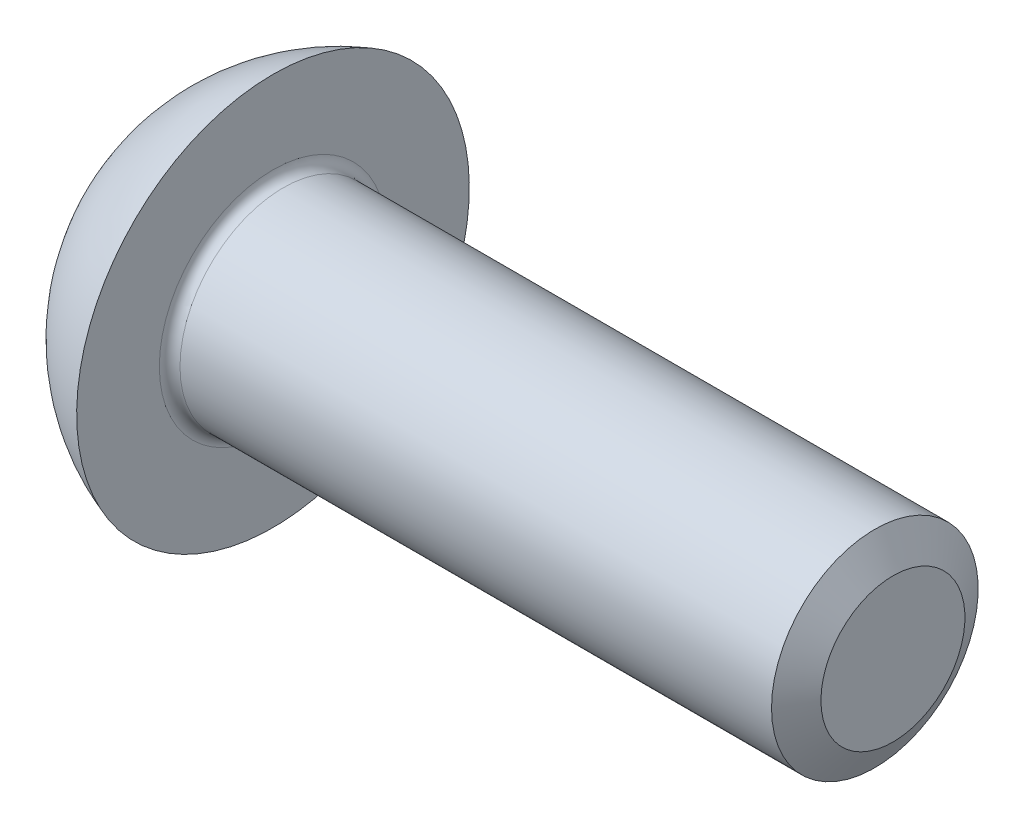
SolidWorks part; units mm, degrees
ref_plane "前视基准面" through (0, 0, 0) normal (0, 0, 1) x (1, 0, 0)
ref_plane "上视基准面" through (0, 0, 0) normal (0, 1, 0) x (1, 0, 0)
ref_plane "右视基准面" through (0, 0, 0) normal (1, 0, 0) x (0, 0, -1)
sketch "尺寸草图" plane through (0, 0, 0) normal (0, 0, 1) x (1, 0, 0)
  line L0 (0, 0) -> (12, 0) construction
  line L1 (12, 0) -> (12, 2) construction
  line L2 (12, 2) -> (11.3, 2) construction
  line L3 (0, 0) -> (0, 3.8) construction
  point P3 (1.4, 0)
  point P6 (12, 2.35)
  point P7 (0, 0.93)
  point P9 (2.2, 0)
  point P10 (2.4, 0)
  point P11 (12, 1.25)
  point P12 (3.7, 0)
  point P13 (4, 0)
  point P14 (12, 14.35)
  dimension "l" = 12
  dimension "d" = 4
  dimension "P" = 0.7
  dimension "a" = 1.4
  dimension "da" = 4.7
  dimension "dk" = 7.6
  dimension "e" = 2.87
  dimension "K" = 2.2
  dimension "r" = 0.2
  dimension "s" = 2.5
  dimension "t" = 1.3
  dimension "w" = 0.3
  dimension "zslwx" = 12
sketch "草图1" plane through (0, 0, 0) normal (0, 0, 1) x (1, 0, 0)
  line L0 (-14.2, 0) -> (0, 0) construction
  line L1 (0, 2) -> (-11.8, 2)
  line L2 (-12, 2.2) -> (-12, 3.8)
  line L3 (-14.2, 0) -> (-14.2, 2)
  line L4 (0, 2) -> (0, 0)
  line L5 (-14.2, 0) -> (0, 0)
  arc A0 (-12, 3.8) -> (-14.2, 2) centre (-10.7273, 0) ccw
  arc A1 (-11.8, 2) -> (-12, 2.2) centre (-11.8, 2.2) cw
  point P10 (-12, 2)
  dimension "r" = 0.2
  dimension "d" = 4
  dimension "dk" = 7.6
  dimension "k" = 2.2
  dimension "l" = 12
revolve "旋转1" add sketch "草图1" angle 360 about L0
cosmetic thread "装饰螺纹线1" parameters "D1"=12, "D2"=3.44
sketch "草图2" plane through (-14.2, 0, 0) normal (-1, 0, 0) x (0, 0, 1)
  line L1 (0, 1.4434) -> (-1.25, 0.7217)
  line L2 (-1.25, 0.7217) -> (-1.25, -0.7217)
  line L3 (-1.25, -0.7217) -> (0, -1.4434)
  line L4 (0, -1.4434) -> (1.25, -0.7217)
  line L5 (1.25, -0.7217) -> (1.25, 0.7217)
  line L6 (1.25, 0.7217) -> (0, 1.4434)
  circle A0 centre (0, 0) radius 1.25 construction
  dimension "s" = 2.5
extrude "切除-拉伸1" cut sketch "草图2" against normal blind 2.2
sketch "草图6" plane through (0, 0, 0) normal (0, 0, 1) x (1, 0, 0)
  line L0 (-12.9, 1.4434) -> (-12, 0)
  line L1 (-11.63, 1.4434) -> (-11.63, 0)
  line L2 (-11.63, 1.4434) -> (-12.9, 1.4434)
  line L3 (-14.2, 0) -> (-12, 0) construction
  line L4 (-11.63, 0) -> (-12, 0)
  line L5 (-14.2, 0) -> (-17.07, 0) construction
  dimension "t" = 1.3
  dimension "e-s" = 0.37
  dimension "k" = 2.2
  dimension "e" = 2.87
revolve "旋转2" add sketch "草图6" angle 360 about L3
sketch "草图7" plane through (0, 0, 0) normal (0, 0, 1) x (1, 0, 0)
  line L3 (-14.2, 1.4434) -> (-13.83, 0)
  line L4 (-14.2, 0) -> (-13.83, 0) construction
  line L7 (-14.2, 1.4434) -> (-14.2, 0)
  line L8 (-14.2, 0) -> (-13.83, 0)
  dimension "e-s" = 0.37
revolve "切除-旋转5" cut sketch "草图7" angle 360 about L4
sketch "草图4" plane through (0, 0, 0) normal (0, 0, 1) x (1, 0, 0)
  line L0 (-0.35, 2) -> (0, 1.3938)
  line L1 (-0.35, 2) -> (0.35, 2)
  line L2 (0.35, 2) -> (0, 1.3938)
  line L4 (0, -2) -> (0, 2) construction
  line L5 (-0.35, 0) -> (0.35, 0) construction
  dimension "d" = 2
  dimension "p" = 0.7
revolve "切除-旋转1" cut sketch "草图4" angle 360 about L5
ref_axis "基准轴1" through (-8.1887, 0, 0) along (1, 0, 0)
pattern_linear "阵列(线性)1" [suppressed] count 15 spacing 0.7 along (-1, 0, 0) of bodies 104
